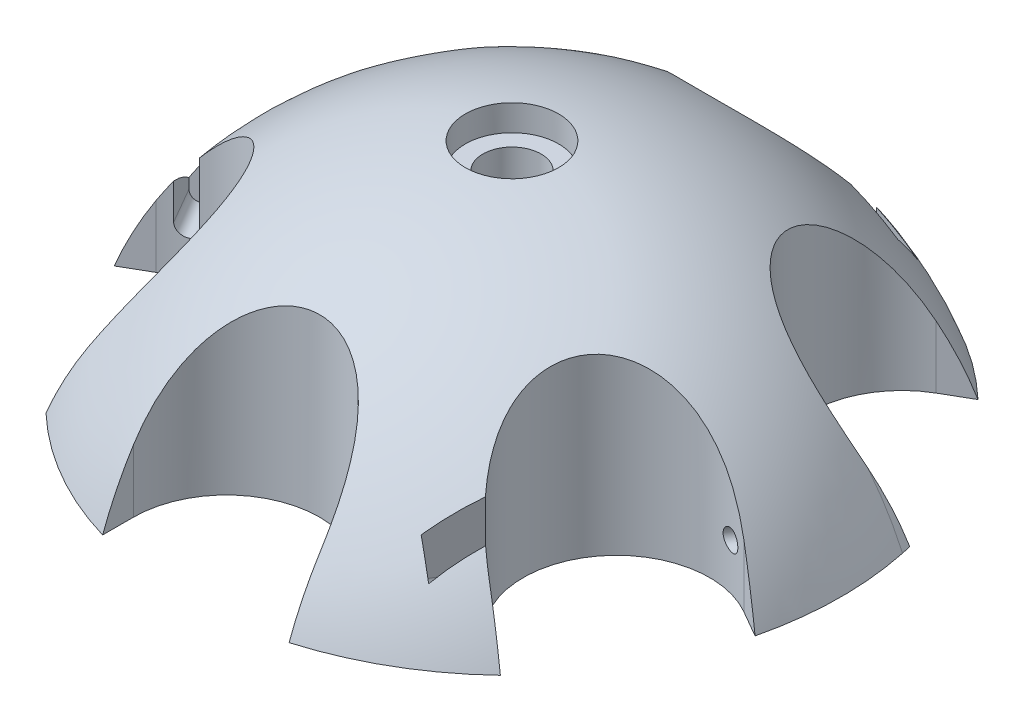
SolidWorks part; units mm, degrees
ref_plane "Front Plane" through (0, 0, 0) normal (0, 0, 1) x (1, 0, 0)
ref_plane "Top Plane" through (0, 0, 0) normal (0, 1, 0) x (1, 0, 0)
ref_plane "Right Plane" through (0, 0, 0) normal (1, 0, 0) x (0, 0, -1)
sketch "Sketch1" plane through (0, 0, 0) normal (0, 0, 1) x (1, 0, 0)
  line L0 (0, 60) -> (0, -60) construction
  line L1 (0, 60) -> (0, -60)
  arc A0 (0, 60) -> (0, -60) centre (0, 0) ccw
  dimension "D1" = 60
revolve "Revolve1" add sketch "Sketch1" angle 360 about L0
ref_plane "Plane4" through (0, 20, 0) normal (0, 1, 0) x (1, 0, 0)
sketch "Sketch2" plane through (0, 20, 0) normal (0, 1, 0) x (1, 0, 0)
  circle A0 centre (0, 0) radius 80.0525
extrude "Cut-Extrude1" cut sketch "Sketch2" against normal through all
ref_axis "Axis2" through (0, 0, 0) along (0, -1, 0)
ref_plane "Plane5" through (0, 0, 0) normal (-0.866, 0, 0.5) x (0, -1, 0)
ref_plane "Plane6" through (0, 0, 0) normal (-0.866, 0, -0.5) x (0, -1, 0)
ref_plane "Plane7" through (0, 0, 0) normal (0, 0, -1) x (0, -1, 0)
sketch "Sketch4" plane through (0, 0, 0) normal (0, 0, -1) x (0, -1, 0)
  line L0 (-20, 62.2254) -> (-20, -62.2254) construction
  arc A0 (-20, 56.5685) -> (-60, 0) centre (0, 0) ccw
  arc A1 (-20, 56.5685) -> (-20, -56.5685) centre (0, 0) ccw construction
sketch "Sketch5" plane through (0, 0, 0) normal (-0.866, 0, -0.5) x (0, -1, 0)
  line L0 (-20, 62.2254) -> (-20, -62.2254) construction
  arc A0 (-20, 56.5685) -> (-60, 0) centre (0, 0) ccw
  arc A1 (-20, 56.5685) -> (-20, -56.5685) centre (0, 0) ccw construction
  ellipse E0 centre (0, 0) end of major axis (-60, 0) minor radius 30 (-20, 28.2843) -> (-60, 0) ccw construction
sketch "Sketch6" plane through (0, 20, 0) normal (0, -1, 0) x (1, 0, 0)
  line L0 (-28.2843, 48.9898) -> (-56.5685, 0) construction
  line L1 (-28.2843, 48.9898) -> (0, 0) construction
  line L2 (-56.5685, 0) -> (0, 0) construction
  line L3 (-29.04, 0) -> (29.04, 0) construction
  line L4 (-42.4264, 24.4949) -> (0, 0) construction
  line L6 (-34.4264, 38.3513) -> (-45.7062, 44.8637)
  line L7 (-50.4264, 10.6385) -> (-61.7062, 17.1509)
  line L8 (-61.7062, 17.1509) -> (-45.7062, 44.8637)
  circle A0 centre (0, 0) radius 56.5685 construction
  arc A1 (-50.4264, 10.6385) -> (-34.4264, 38.3513) centre (-42.4264, 24.4949) ccw
  dimension "D1" = 16
extrude "Cut-Extrude2" cut sketch "Sketch6" against normal through all
pattern_circular "CirPattern1" count 6 over 360 about axis through (0, 0, 0) along (0, -1, 0) of "Cut-Extrude2"
sketch "Sketch7" plane through (8, 0, 13.8564) normal (-0.5, 0, -0.866) x (-0.866, 0, 0.5)
  line L0 (32.9898, 20) -> (48.9898, 20) construction
  line L1 (0, 0) -> (0, -52.8) construction
  circle A0 centre (45, 28) radius 1.75
  dimension "D1" = 3.5
  dimension "D2" = 8
  dimension "D3" = 45
extrude "Cut-Extrude3" cut sketch "Sketch7" against normal blind 3 and the other way blind 39
ref_plane "Plane11" through (0, 0, 0) normal (-0.5, 0, -0.866) x (-0.866, 0, 0.5)
sketch "Sketch11" plane through (0, 0, 0) normal (-0.5, 0, -0.866) x (-0.866, 0, 0.5)
  line L0 (46.75, 28) -> (46.75, 40.6459)
  line L1 (46.75, 40.6459) -> (43.25, 40.6459)
  line L2 (43.25, 40.6459) -> (43.25, 28)
  arc A0 (43.25, 28) -> (46.75, 28) centre (45, 28) ccw
  dimension "D1" = 3.5
extrude "Cut-Extrude5" cut sketch "Sketch11" along normal up to surface (23 mm away) up to face at (-51.9867, 28, 3.4564)
pattern_circular "CirPattern2" count 3 every 120 about axis through (0, 0, 0) along (0, -1, 0) of "Cut-Extrude5", "Cut-Extrude3"
sketch "Sketch12" plane through (0, 20, 0) normal (0, -1, 0) x (1, 0, 0)
  line L1 (15.5885, -27) -> (31.1769, 0)
  line L2 (31.1769, 0) -> (15.5885, 27)
  line L3 (15.5885, 27) -> (-15.5885, 27)
  line L4 (-15.5885, 27) -> (-31.1769, 0)
  line L5 (-31.1769, 0) -> (-15.5885, -27)
  line L6 (-15.5885, -27) -> (15.5885, -27)
  circle A0 centre (0, 0) radius 27 construction
  dimension "D1" = 54
ref_plane "Plane12" through (0, 60, 0) normal (0, 1, 0) x (1, 0, 0)
sketch "Sketch14" plane through (0, 60, 0) normal (0, 1, 0) x (1, 0, 0)
  circle A0 centre (0, 0) radius 8
  dimension "D1" = 16
extrude "Cut-Extrude8" cut sketch "Sketch14" against normal blind 5
extrude "Boss-Extrude1" add sketch "Sketch12" along normal blind 4
sketch "Sketch13" plane through (0, 60, 0) normal (0, 1, 0) x (1, 0, 0)
  circle A0 centre (0, 0) radius 5
  dimension "D1" = 10
extrude "Cut-Extrude7" cut sketch "Sketch13" against normal through all
